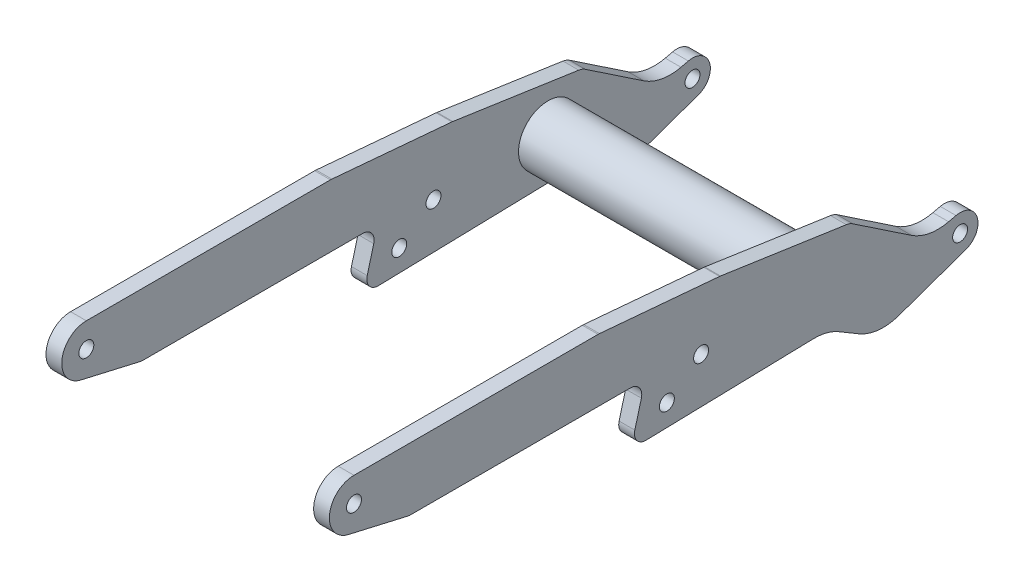
SolidWorks part; units mm, degrees
ref_plane "Front Plane" through (0, 0, 0) normal (0, 0, 1) x (1, 0, 0)
ref_plane "Top Plane" through (0, 0, 0) normal (0, 1, 0) x (1, 0, 0)
ref_plane "Right Plane" through (0, 0, 0) normal (1, 0, 0) x (0, 0, -1)
sketch "Sketch1" plane through (0, 0, 0) normal (1, 0, 0) x (0, 0, -1)
  line L0 (0, 6.25) -> (0, 0) construction
  line L1 (0, 0) -> (79.4049, 0) construction
  line L2 (0, 3.125) -> (31.1, 3.125)
  line L3 (31.1, 3.125) -> (46.5, 1.7777)
  line L4 (46.5, 1.7777) -> (63, -0.6441)
  line L5 (70.831, -5.8964) -> (63, -0.6441)
  line L6 (76.4807, -6.5351) -> (75.5428, -6.755)
  line L7 (-0.703, -3.0449) -> (7, -4.8233)
  line L8 (7, -4.8233) -> (35.1103, -4.8233)
  line L9 (36.5109, -6.6486) -> (35.68, -9.7495)
  line L10 (37.1171, -11.5743) -> (58.3801, -11.0398)
  line L11 (77.7572, -10.8953) -> (69.2368, -13.9025)
  line L13 (64.1893, -13.4111) -> (61.5815, -11.8713)
  circle A0 centre (0, 0) radius 0.95
  circle A1 centre (77, -8.75) radius 0.95
  circle A2 centre (39.75, -8.75) radius 0.95
  circle A3 centre (44.1, -5.6) radius 0.95
  arc A4 (0, 3.125) -> (-0.703, -3.0449) centre (0, 0) ccw
  arc A5 (76.4807, -6.5351) -> (77.7572, -10.8953) centre (77, -8.75) cw
  arc A6 (58.3801, -11.0398) -> (61.5815, -11.8713) centre (58.5309, -17.0379) cw
  arc A7 (69.2368, -13.9025) -> (64.1893, -13.4111) centre (67.2399, -8.2445) cw
  arc A8 (75.5428, -6.755) -> (70.831, -5.8964) centre (74.1731, -0.9134) cw
  arc A9 (37.1171, -11.5743) -> (35.68, -9.7495) centre (37.0806, -10.1248) cw
  arc A10 (35.1103, -4.8233) -> (36.5109, -6.6486) centre (35.1103, -6.2733) cw
  point P26 (60.1, -10.9966)
  point P31 (73, -7.3512)
  point P36 (37, -4.8233)
  dimension "D1" = 1.9
  dimension "D8" = 3.125
  dimension "D9" = 2.275
  dimension "D25" = 6
  dimension "D26" = 1.45
  dimension "D2" = 39.75
  dimension "D3" = 8.75
  dimension "D4" = 44.1
  dimension "D5" = 5.6
  dimension "D6" = 77
  dimension "D7" = 8.75
  dimension "D10" = 31.1
  dimension "D11" = 46.5
  dimension "D12" = 63
  dimension "D13" = 175
  dimension "D14" = 176.65
  dimension "D15" = 154.5
  dimension "D16" = 10
  dimension "D17" = 7
  dimension "D18" = 167
  dimension "D19" = 30
  dimension "D20" = 75
  dimension "D21" = 73.56
  dimension "D22" = 16
  dimension "D23" = 148
  dimension "D24" = 130
extrude "Boss-Extrude1" add sketch "Sketch1" along normal mid plane 36
fillet "Fillet1" radius 2 4 edges at (0, -4.8233, -7) (0, -0.6441, -63) (0, 1.7777, -46.5) (0, 3.125, -31.1)
sketch "Sketch2" plane through (0, 0, 0) normal (0, 1, 0) x (1, 0, 0)
  line L0 (-18, 46.4417) -> (-18, 31.187) construction
  line L1 (-16, 89.9285) -> (16, 89.9285)
  line L2 (-16, 89.9285) -> (-16, -12.0292)
  line L3 (-16, -12.0292) -> (16, -12.0292)
  line L4 (16, 89.9285) -> (16, -12.0292)
  line L5 (-16, 89.9285) -> (16, -12.0292) construction
  line L6 (-16, -12.0292) -> (16, 89.9285) construction
  line L7 (18, 46.4417) -> (18, 31.187) construction
  point P0 (0, 38.9496)
  dimension "D1" = 2
  dimension "D2" = 2
extrude "Cut-Extrude1" cut sketch "Sketch2" against normal through all both and the other way through all
sketch "Sketch3" plane through (0, 0, 0) normal (1, 0, 0) x (0, 0, -1)
  circle A0 centre (58.65, -5.75) radius 3.75
  dimension "D1" = 7.5
  dimension "D2" = 58.65
  dimension "D3" = 5.75
extrude "Boss-Extrude2" add sketch "Sketch3" along normal up to next (16 mm away) and the other way up to next (16 mm away)
